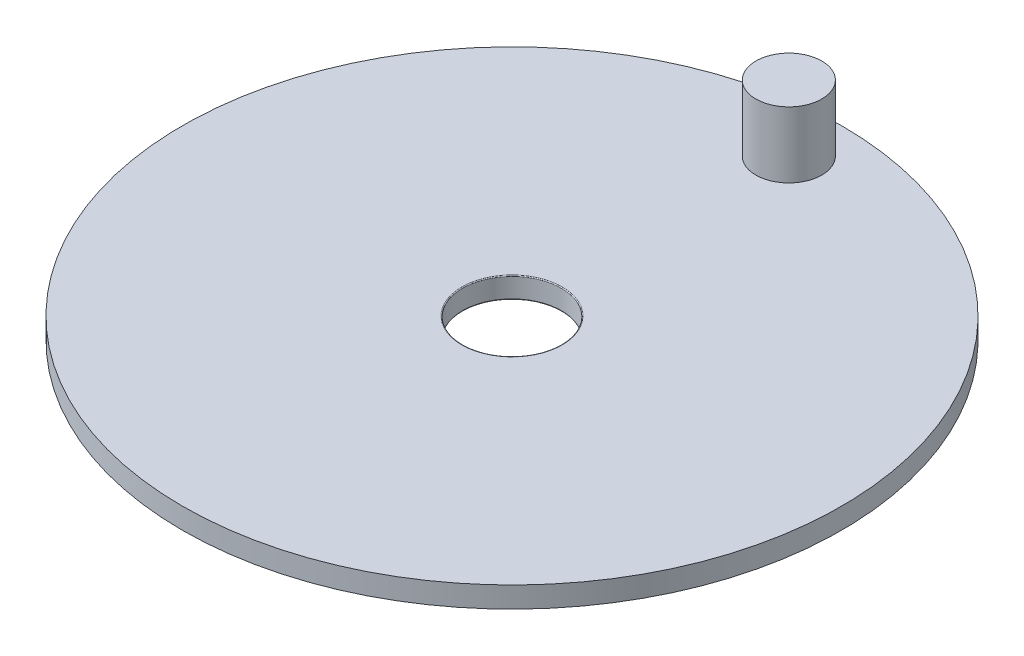
SolidWorks part; units mm, degrees
ref_plane "Front Plane" through (0, 0, 0) normal (0, 0, 1) x (1, 0, 0)
ref_plane "Top Plane" through (0, 0, 0) normal (0, 1, 0) x (1, 0, 0)
ref_plane "Right Plane" through (0, 0, 0) normal (1, 0, 0) x (0, 0, -1)
ref_axis "X Axis" through (-91.3614, 0, 0) along (1, 0, 0)
ref_axis "Z Axis" through (0, 0, 55) along (0, 0, -1)
ref_axis "Y Axis" through (0, 67.9804, 0) along (0, -1, 0)
sketch "Sketch1" plane through (0, 0, 0) normal (0, 1, 0) x (1, 0, 0)
  circle A0 centre (0, 0) radius 50
  dimension "D1" = 100
extrude "Boss-Extrude1" add sketch "Sketch1" along normal blind 3.175
sketch "Sketch2" plane through (0, 3.175, 0) normal (0, 1, 0) x (1, 0, 0)
  circle A0 centre (-15.875, 0) radius 1.5875
  dimension "D1" = 3.175
  dimension "D2" = 15.875
sketch "Sketch3" plane through (0, 3.175, 0) normal (0, 1, 0) x (1, 0, 0)
  circle A0 centre (0, 0) radius 7.5
  dimension "D1" = 15
extrude "Cut-Extrude1" cut sketch "Sketch3" against normal through all
fillet "Fillet3" radius 0.127 2 edges at (0, 0, 7.5) (0, 3.175, 7.5)
sketch "Sketch4" plane through (0, 3.175, 0) normal (0, 1, 0) x (1, 0, 0)
  circle A0 centre (0, 42) radius 5
  dimension "D1" = 42
  dimension "10" = 10
extrude "Boss-Extrude2" add sketch "Sketch4" along normal blind 10
